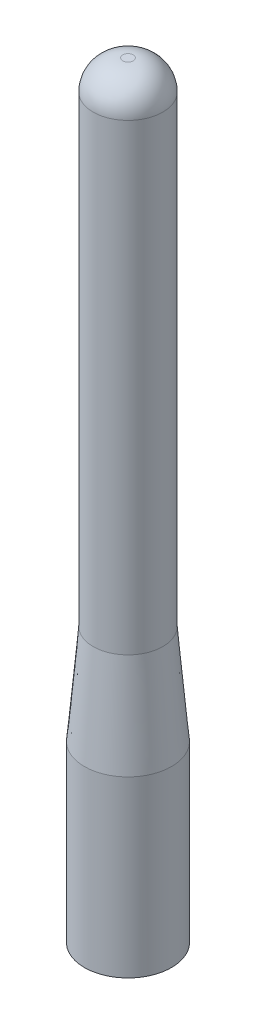
SolidWorks part; units mm, degrees
ref_plane "Front Plane" through (0, 0, 0) normal (0, 0, 1) x (1, 0, 0)
ref_plane "Top Plane" through (0, 0, 0) normal (0, 1, 0) x (1, 0, 0)
ref_plane "Right Plane" through (0, 0, 0) normal (1, 0, 0) x (0, 0, -1)
sketch "Sketch1" plane through (0, 0, 0) normal (0, 1, 0) x (1, 0, 0)
  circle A0 centre (0, 0) radius 5
extrude "Boss-Extrude1" add sketch "Sketch1" along normal blind 20
sketch "Sketch2" plane through (0, 20, 0) normal (0, 1, 0) x (1, 0, 0)
  circle A0 centre (0, 0) radius 4
extrude "Boss-Extrude2" add sketch "Sketch2" along normal blind 68
fillet "Fillet1" radius 3.4 1 edges at (0, 88, 4)
chamfer "Chamfer1" distance 1 angle 85 1 edges at (0, 20, 4) first distance on face at (0, 20, 4)
sketch "Sketch3" plane through (0, 0, 0) normal (0, -1, 0) x (-1, 0, 0)
  line L1 (-2.5, -2.5) -> (2.5, -2.5)
  line L2 (-2.5, -2.5) -> (-2.5, 2.5)
  line L3 (-2.5, 2.5) -> (2.5, 2.5)
  line L4 (2.5, -2.5) -> (2.5, 2.5)
  line L5 (-2.5, -2.5) -> (2.5, 2.5) construction
  line L6 (-2.5, 2.5) -> (2.5, -2.5) construction
  point P0 (0, 0)
  point P8 (0.282, 2.5)
  dimension "D1" = 5
  dimension "D2" = 5
  dimension "D3" = 5
extrude "Cut-Extrude1" cut sketch "Sketch3" against normal blind 8
sketch "Sketch4" plane through (0, 0, 0) normal (0, -1, 0) x (-1, 0, 0)
  line L1 (2.5, 2.5) -> (-2.5, 2.5)
  line L2 (2.5, 2.5) -> (2.5, 5.2024)
  line L3 (2.5, 5.2024) -> (-2.5, 5.2024)
  line L4 (-2.5, 2.5) -> (-2.5, 5.2024)
  dimension "D1" = 5
extrude "Cut-Extrude2" cut sketch "Sketch4" against normal blind 8
sketch "Sketch5" plane through (2.5, 0, 0) normal (-1, 0, 0) x (0, 0, 1)
  circle A0 centre (0, 5.5) radius 0.5
  point P2 (0, 0)
extrude "Boss-Extrude3" add sketch "Sketch5" along normal blind 5
